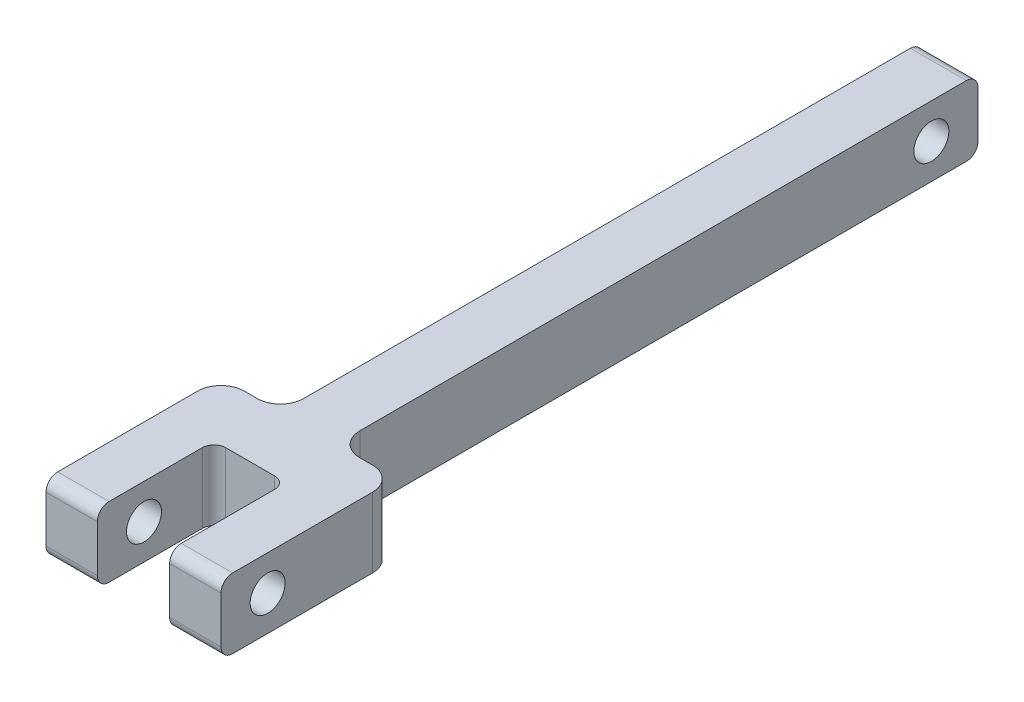
SolidWorks part; units mm, degrees
ref_plane "Alzado" through (0, 0, 0) normal (0, 0, 1) x (1, 0, 0)
ref_plane "Planta" through (0, 0, 0) normal (0, 1, 0) x (1, 0, 0)
ref_plane "Vista lateral" through (0, 0, 0) normal (1, 0, 0) x (0, 0, -1)
sketch "Croquis1" plane through (0, 0, 0) normal (1, 0, 0) x (0, 0, -1)
  line L0 (-34, 3) -> (34, 3)
  line L2 (-35, 0) -> (35, 0) construction
  line L3 (-35, 2) -> (-35, -2)
  line L4 (-34, -3) -> (34, -3)
  line L5 (35, 2) -> (35, -2)
  arc A0 (-35, -2) -> (-34, -3) centre (-34, -2) ccw
  arc A1 (-35, 2) -> (-34, 3) centre (-34, 2) cw
  arc A2 (34, -3) -> (35, -2) centre (34, -2) ccw
  arc A3 (34, 3) -> (35, 2) centre (34, 2) cw
  point P1 (0, 0)
  point P9 (-35, -3)
  point P13 (-35, 3)
  point P16 (35, -3)
  point P19 (35, 3)
  dimension "D3" = 1
  dimension "D4" = 1
  dimension "D1" = 3
  dimension "D2" = 70
extrude "Saliente-Extruir1" add sketch "Croquis1" along normal mid plane 4.8
sketch "Croquis2" plane through (0, 0, 0) normal (1, 0, 0) x (0, 0, -1)
  line L0 (-35, 2) -> (-35, -2) construction
  line L1 (35, -2) -> (35, 2) construction
  circle A0 centre (-31, 0) radius 1.5
  circle A1 centre (31, 0) radius 1.5
  dimension "D1" = 3
  dimension "D3" = 3
  dimension "D2" = 4
  dimension "D4" = 4
extrude "Cortar-Extruir1" cut sketch "Croquis2" against normal through all both and the other way through all
sketch "Croquis3" plane through (0, 0, 0) normal (1, 0, 0) x (0, 0, -1)
  line L0 (-35, 2) -> (-35, -2) construction
  line L1 (-35, 2) -> (-35, -2)
  line L2 (-34, 3) -> (-20, 3)
  line L3 (34, 3) -> (-34, 3) construction
  line L4 (-20, 3) -> (-20, -3)
  line L5 (-34, -3) -> (34, -3) construction
  line L6 (-20, -3) -> (-34, -3)
  circle A0 centre (-31, 0) radius 1.5 construction
  circle A1 centre (-31, 0) radius 1.5
  arc A2 (-34, 3) -> (-35, 2) centre (-34, 2) ccw construction
  arc A3 (-34, 3) -> (-35, 2) centre (-34, 2) ccw
  arc A4 (-35, -2) -> (-34, -3) centre (-34, -2) ccw construction
  arc A5 (-35, -2) -> (-34, -3) centre (-34, -2) ccw
  dimension "D1" = 15
extrude "Saliente-Extruir2" add sketch "Croquis3" along normal mid plane 15
sketch "Croquis4" plane through (0, 0, 0) normal (1, 0, 0) x (0, 0, -1)
  line L0 (-34, 3) -> (-25, 3)
  line L1 (-20, 3) -> (-34, 3) construction
  line L2 (-25, 3) -> (-25, -3)
  line L3 (-34, -3) -> (-20, -3) construction
  line L4 (-35, 2) -> (-35, -2)
  line L5 (-34, -3) -> (-20, -3)
  line L6 (-20, -3) -> (-20, 3)
  line L7 (-20, 3) -> (-34, 3)
  line L8 (-35, 2) -> (-35, -2)
  line L12 (-25, -3) -> (-34, -3)
  arc A2 (-34, 3) -> (-35, 2) centre (-34, 2) ccw
  arc A3 (-35, -2) -> (-34, -3) centre (-34, -2) ccw
  arc A4 (-34, 3) -> (-35, 2) centre (-34, 2) ccw
  arc A5 (-35, -2) -> (-34, -3) centre (-34, -2) ccw
  dimension "D2" = 10
  dimension "D1" = 0
extrude "Cortar-Extruir2" cut sketch "Croquis4" against normal mid plane 6.2
fillet "Redondeo1" radius 2 4 edges at (2.4, 0, 20) (-2.4, 0, 20) (7.5, 0, 20) (-7.5, 0, 20)
fillet "Redondeo2" radius 1 2 edges at (3.1, 0, 25) (-3.1, 0, 25)
